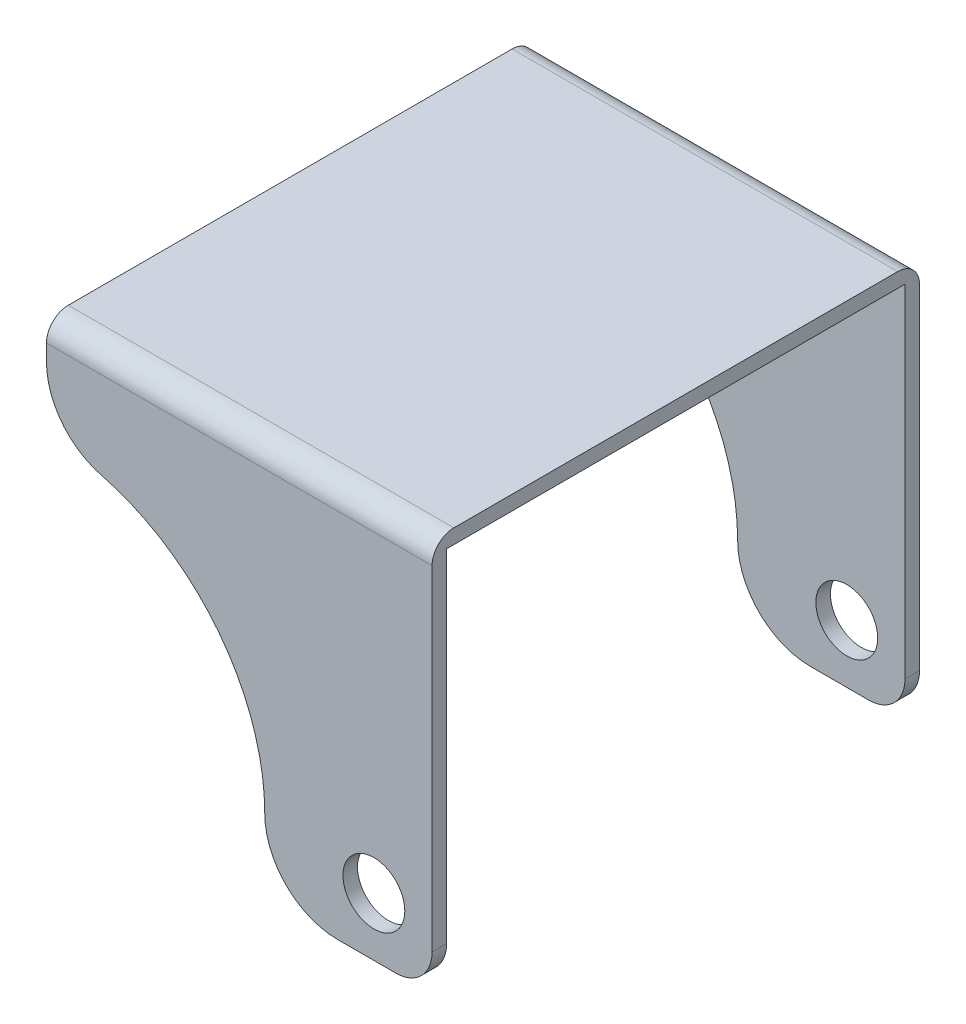
SolidWorks part; units mm, degrees
ref_plane "Front Plane" through (0, 0, 0) normal (0, 0, 1) x (1, 0, 0)
ref_plane "Top Plane" through (0, 0, 0) normal (0, 1, 0) x (1, 0, 0)
ref_plane "Right Plane" through (0, 0, 0) normal (1, 0, 0) x (0, 0, -1)
sketch "Sketch1" plane through (0, 0, 0) normal (0, 0, 1) x (1, 0, 0)
  line L0 (-27.5, 14.5152) -> (-27.5, 17.7854)
  line L1 (-27.5, 17.7854) -> (25.5, 17.7854)
  line L2 (25.5, 17.7854) -> (25.5, -34.2146)
  line L3 (25.5, -34.2146) -> (12.5, -34.2146)
  line L4 (20.5, -34.2146) -> (-27.5, -34.2146) construction
  arc A0 (2.5, -24.2146) -> (-20, 4.8328) centre (-27.5, -24.2146) ccw
  arc A1 (-20, 4.8328) -> (-27.5, 14.5152) centre (-17.5, 14.5152) cw
  arc A2 (12.5, -34.2146) -> (2.5, -24.2146) centre (12.5, -24.2146) cw
  point P11 (-27.5, 5.7854)
  point P14 (0.7843, -34.2146)
  dimension "D1" = 53
  dimension "D3" = 30
  dimension "D4" = 10
  dimension "D5" = 10
  dimension "D2" = 52
extrude "Boss-Extrude1" add sketch "Sketch1" along normal blind 2
fillet "Fillet1" radius 5 1 edges at (25.5, -34.2146, 1)
sketch "Sketch2" plane through (0, 0, 2) normal (0, 0, 1) x (1, 0, 0)
  line L0 (25.5, -29.2146) -> (25.5, 17.7854) construction
  line L1 (12.5, -34.2146) -> (20.5, -34.2146) construction
  circle A0 centre (17.5, -26.2146) radius 4.25
  dimension "D1" = 8.5
  dimension "D2" = 8
  dimension "D3" = 8
extrude "Cut-Extrude1" cut sketch "Sketch2" against normal blind 10
ref_plane "Plane1" through (0, 0, -31.5) normal (0, 0, -1) x (-1, 0, 0)
mirror "Mirror3" about plane through (0, 0, -31.5) normal (0, 0, -1) of bodies 102
sketch "Sketch3" plane through (0, 17.7854, 0) normal (0, 1, 0) x (1, 0, 0)
  line L1 (-27.5, 65) -> (25.5, 65)
  line L2 (-27.5, 65) -> (-27.5, -2)
  line L3 (-27.5, -2) -> (25.5, -2)
  line L4 (25.5, 65) -> (25.5, -2)
extrude "Boss-Extrude2" add sketch "Sketch3" along normal blind 2
fillet "Fillet2" radius 3 2 edges at (-1, 19.7854, 2) (-1, 19.7854, -65)
